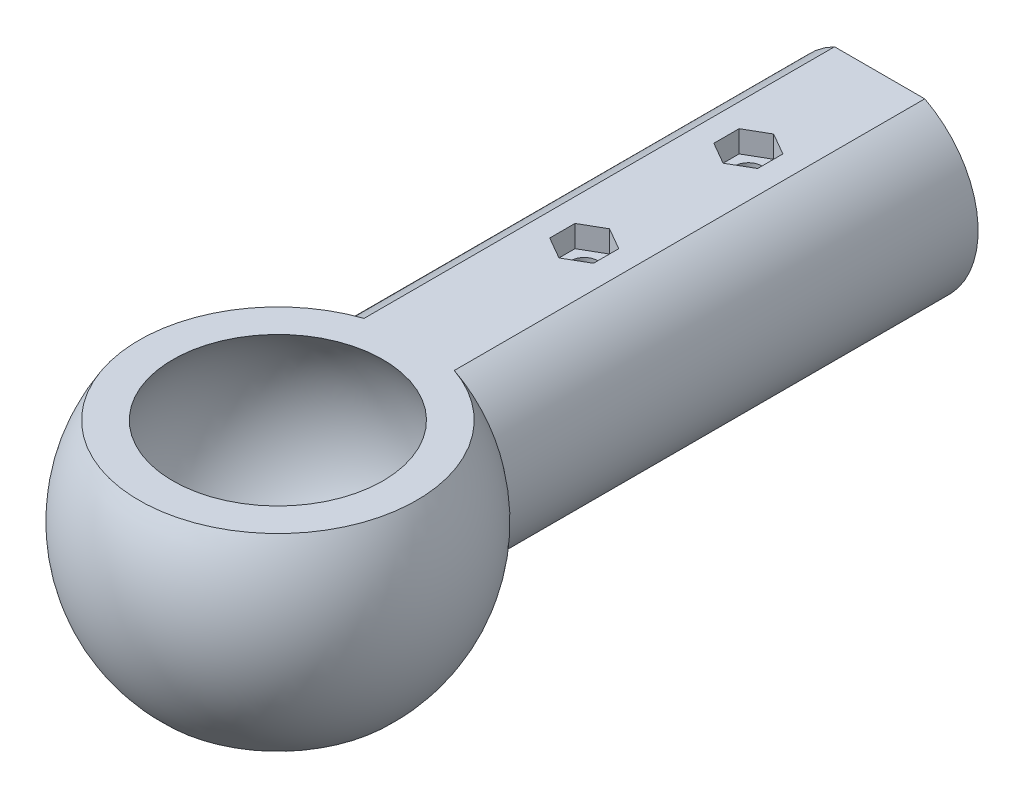
SolidWorks part; units mm, degrees
ref_plane "Front Plane" through (0, 0, 0) normal (0, 0, 1) x (1, 0, 0)
ref_plane "Top Plane" through (0, 0, 0) normal (0, 1, 0) x (1, 0, 0)
ref_plane "Right Plane" through (0, 0, 0) normal (1, 0, 0) x (0, 0, -1)
sketch "Sketch1" plane through (0, 0, 0) normal (0, 0, 1) x (1, 0, 0)
  line L0 (0, 10) -> (0, -10) construction
  line L1 (2.8, 8) -> (8.2614, 8) construction
  line L2 (2.8, -11) -> (3.3541, -11) construction
  line L3 (0, 0) -> (15, 0) construction
  line L4 (9.6047, 8) -> (12.6886, 8)
  line L5 (5.9372, -11) -> (10.198, -11)
  line L6 (2.8, 8) -> (2.8, -5.866) construction
  line L7 (2.8, -5.866) -> (2.8, -11) construction
  arc A0 (10.198, -11) -> (12.6886, 8) centre (0, 0) ccw
  arc A1 (5.9372, -11) -> (9.6047, 8) centre (0, 0) ccw
  arc A2 (3.3541, -11) -> (8.2614, 8) centre (0, 0) ccw construction
  dimension "D1" = 15
  dimension "D2" = 12.5
  dimension "D3" = 11.5
  dimension "D4" = 8
  dimension "D6" = 11
  dimension "D7" = 2.8
revolve "Revolve1" add sketch "Sketch1" angle 360 about L0 region at (11.1466, 7.7895, 0)
ref_plane "Plane1" through (0, 0, -15) normal (0, 0, -1) x (-1, 0, 0)
sketch "Sketch2" plane through (0, 0, -15) normal (0, 0, -1) x (-1, 0, 0)
  line L0 (4.1231, 8) -> (-4.1231, 8)
  arc A2 (-4.1231, 8) -> (4.1231, 8) centre (0, 0) ccw
  dimension "D1" = 18
  dimension "D2" = 8
extrude "Boss-Extrude2" add sketch "Sketch2" along normal blind 40 and the other way up to next contours L0 A2 region at (0, -0.1877, -15)
sketch "Sketch3" plane through (0, 0, -55) normal (0, 0, -1) x (-1, 0, 0)
  circle A0 centre (0, 0) radius 3.25
  dimension "D1" = 6.5
extrude "Cut-Extrude1" cut sketch "Sketch3" against normal blind 35
sketch "Sketch4" plane through (0, 8, 0) normal (0, 1, 0) x (1, 0, 0)
  line L0 (0, 0) -> (0, 55) construction
  line L1 (-4.1231, 55) -> (4.1231, 55) construction
  line L3 (2, 41.8453) -> (2, 44.1547)
  line L4 (2, 44.1547) -> (0, 45.3094)
  line L5 (0, 45.3094) -> (-2, 44.1547)
  line L6 (-2, 44.1547) -> (-2, 41.8453)
  line L7 (-2, 41.8453) -> (0, 40.6906)
  line L8 (0, 40.6906) -> (2, 41.8453)
  line L9 (2, 26.8453) -> (2, 29.1547)
  line L10 (2, 29.1547) -> (0, 30.3094)
  line L11 (0, 30.3094) -> (-2, 29.1547)
  line L12 (-2, 29.1547) -> (-2, 26.8453)
  line L13 (-2, 26.8453) -> (0, 25.6906)
  line L14 (0, 25.6906) -> (2, 26.8453)
  circle A0 centre (0, 43) radius 2 construction
  circle A1 centre (0, 28) radius 2 construction
  circle A2 centre (0, 43) radius 1.25
  circle A3 centre (0, 28) radius 1.25
  dimension "D1" = 4
  dimension "D2" = 4
  dimension "D5" = 2.5
  dimension "D6" = 2.5
  dimension "D3" = 15
  dimension "D4" = 12
extrude "Cut-Extrude3" cut sketch "Sketch4" against normal blind 2 contours L13 L14 L9 L10 L11 L12 A3 | L7 L8 L3 L4 L5 L6 A2 region at (0.9694, 8, -41.3209) region at (0.9694, 8, -26.3209)
extrude "Cut-Extrude4" cut sketch "Sketch4<3>" against normal up to next contours A3 | A2 region at (0, 8, -43) region at (0, 8, -28)
sketch "Sketch4<3>" plane through (0, 8, 0) normal (0, 1, 0) x (1, 0, 0) same geometry as "Sketch4"
